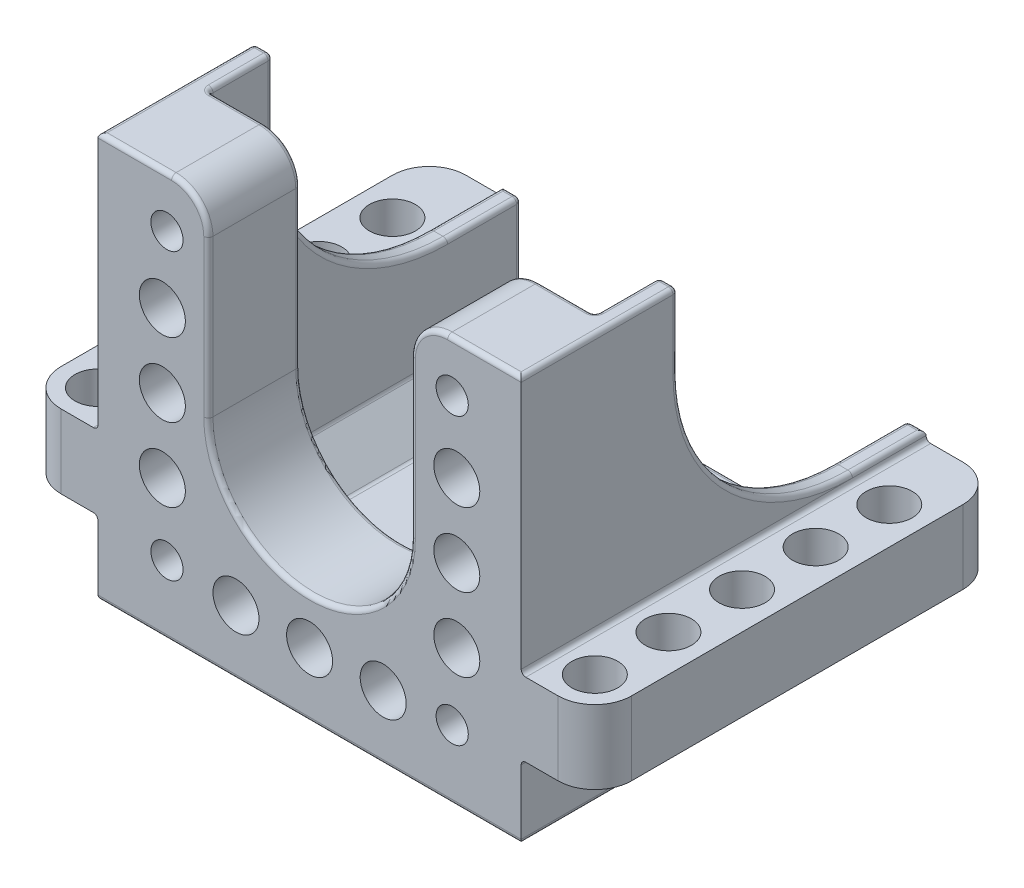
SolidWorks part; units mm, degrees
ref_plane "Front Plane" through (0, 0, 0) normal (0, 0, 1) x (1, 0, 0)
ref_plane "Top Plane" through (0, 0, 0) normal (0, 1, 0) x (1, 0, 0)
ref_plane "Right Plane" through (0, 0, 0) normal (1, 0, 0) x (0, 0, -1)
sketch "Sketch1" plane through (0, 0, 0) normal (0, 0, 1) x (1, 0, 0)
  line L0 (-16, 0) -> (16, 0) construction
  line L1 (-21, -21) -> (21, -21)
  line L2 (-21, -21) -> (-21, 21)
  line L3 (-21, 21) -> (-11, 21)
  line L4 (21, -21) -> (21, 21)
  line L5 (-21, -21) -> (21, 21) construction
  line L6 (-21, 21) -> (21, -21) construction
  line L7 (-8, -16) -> (8, -16) construction
  line L8 (0, -16) -> (0, 0) construction
  line L9 (-11, 0) -> (-11, 21)
  line L10 (16, -8) -> (16, 8) construction
  line L11 (11, 0) -> (11, 21)
  line L12 (-16, 8) -> (-16, -8) construction
  line L13 (11, 21) -> (21, 21)
  line L14 (21, 21) -> (23, 21)
  line L15 (23, 21) -> (23, -23)
  line L16 (23, -23) -> (-23, -23)
  line L17 (-23, -23) -> (-23, 21)
  line L18 (-23, 21) -> (-21, 21)
  circle A0 centre (-15.5, -15.5) radius 1.75
  circle A1 centre (-15.5, 15.5) radius 1.75
  circle A2 centre (15.5, 15.5) radius 1.75
  circle A3 centre (15.5, -15.5) radius 1.75
  circle A4 centre (16, 0) radius 2.5
  circle A5 centre (-16, 0) radius 2.5
  circle A6 centre (0, -16) radius 2.5
  arc A7 (-11, 0) -> (11, 0) centre (0, 0) ccw
  circle A8 centre (16, 8) radius 2.5
  circle A9 centre (16, -8) radius 2.5
  circle A10 centre (8, -16) radius 2.5
  circle A11 centre (-8, -16) radius 2.5
  circle A12 centre (-16, -8) radius 2.5
  circle A13 centre (-16, 8) radius 2.5
  point P0 (0, 0)
  dimension "D4" = 11
  dimension "D5" = 3.5
  dimension "D6" = 2
  dimension "D8" = 5
  dimension "D1" = 31
  dimension "D2" = 31
  dimension "D3" = 42
  dimension "D7" = 2
  dimension "D9" = 16
  dimension "D10" = 32
  dimension "D11" = 16
extrude "Boss-Extrude1" add sketch "Sketch1" along normal blind 10 contours A7 L9 L3 L2 L1 L4 L13 L11 A13 A12 A11 A10 A9 A8 A6 A5 A4 A3 A2 A1 A0 | L18 L17 L16 L15 L14 L4 L1 L2 region at (-20.406, 0, 0) region at (0, -21.6366, 0)
extrude "Boss-Extrude2" add sketch "Sketch1<3>" against normal blind 34 contours L18 L17 L16 L15 L14 L4 L1 L2 region at (0, -21.6366, 0)
sketch "Sketch1<3>" plane through (0, 0, 0) normal (0, 0, 1) x (1, 0, 0) same geometry as "Sketch1"
sketch "Sketch3" plane through (23, 0, 0) normal (1, 0, 0) x (0, 0, -1)
  line L0 (7, 21) -> (7, 13)
  line L1 (-10, 21) -> (34, 21) construction
  line L2 (-10, 21) -> (-10, -23) construction
  line L3 (26, -6) -> (34, -6)
  line L4 (34, 21) -> (34, -23) construction
  line L5 (-10, -15) -> (34, -15)
  line L6 (-10, -15) -> (-10, -7)
  line L7 (-10, -7) -> (34, -7)
  line L8 (34, -15) -> (34, -7)
  line L9 (-10, -23) -> (34, -23) construction
  arc A0 (7, 13) -> (26, -6) centre (26, 13) ccw
  line M2 (34, -23) -> (34, 21)
  line M3 (34, 21) -> (-10, 21)
  line M4 (-10, 21) -> (-10, -23)
  dimension "D1" = 8
  dimension "D2" = 8
  dimension "D3" = 1
  dimension "D4" = 8
extrude "Cut-Extrude1" cut sketch "Sketch3" against normal through all contours L0 A0 L3 M2 M3 region at (23, 8.6006, -21.6006)
extrude "Boss-Extrude3" add sketch "Sketch3<3>" along normal blind 8 contours L7 L5 M4 M2 region at (23, -11, -12)
sketch "Sketch3<3>" plane through (23, 0, 0) normal (1, 0, 0) x (0, 0, -1) same geometry as "Sketch3"
sketch "Sketch4" plane through (0, -7, 0) normal (0, 1, 0) x (1, 0, 0)
  line L0 (31, -10) -> (31, 34) construction
  line L1 (31, -10) -> (23, -10) construction
  circle A0 centre (27, -5.999) radius 2.5
  circle A1 centre (27, 2.001) radius 2.5
  circle A2 centre (27, 10.001) radius 2.5
  circle A3 centre (27, 18.001) radius 2.5
  circle A4 centre (27, 26.001) radius 2.5
  point P14 (0, 0)
  dimension "D1" = 5
  dimension "D4" = 4.001
  dimension "D3" = 4
  dimension "D5" = 32
  dimension "D2" = 5
extrude "Cut-Extrude2" cut sketch "Sketch4" against normal through all
mirror "Mirror1" about plane through (0, 0, 0) normal (1, 0, 0) of "Cut-Extrude2", "Boss-Extrude3"
chamfer "Chamfer1" distance 4 angle 45 2 edges at (-21, -21, -17) (21, -21, -17)
fillet "Fillet1" radius 0.5 52 edges at (-11, 10.5, 10) (0, -11, 10) (-11, 10.5, 0) (0, -11, 0) (-23, 17, -7) (-23, -6, -30) (-21, -6, -30) (-21, -0.435, -12.565) (23, 17, -7) (23, -6, -30) (21, 17, -7) (21, -6, -30) (0, -23, 10) (23, -23, -12) (0, -23, -34) (-23, -23, -12) (0, -21, -34) (-21, -11.5, -34) (21, -11.5, -34) (11, 10.5, 10) (-17, 21, 10) (17, 21, 10) (23, 21, 1.5) (-23, 21, 1.5) (11, 10.5, 0) (22, -6, -34) (-22, -6, -34) (-23, -0.435, -12.565) (-21, 17, -7) (-22, 21, -7) (22, 21, -7) (23, -0.435, -12.565) (21, -0.435, -12.565) (0, -21, 0) (17, -21, -17) (-17, -21, -17) (19, -19, 0) (21, -17, -17) (-19, -19, 0) (-21, -17, -17) (19, -19, -34) (-19, -19, -34)
fillet "Fillet2" radius 4 10 edges at (-11.1464, 20.8536, 0.1464) (-11.1464, 20.8536, 9.8536) (11.1464, 20.8536, 0.1464) (11.1464, 20.8536, 9.8536) (-31, -11, -34) (-31, -11, 10) (31, -11, -34) (31, -11, 10) (11, 21, 5) (-11, 21, 5)
